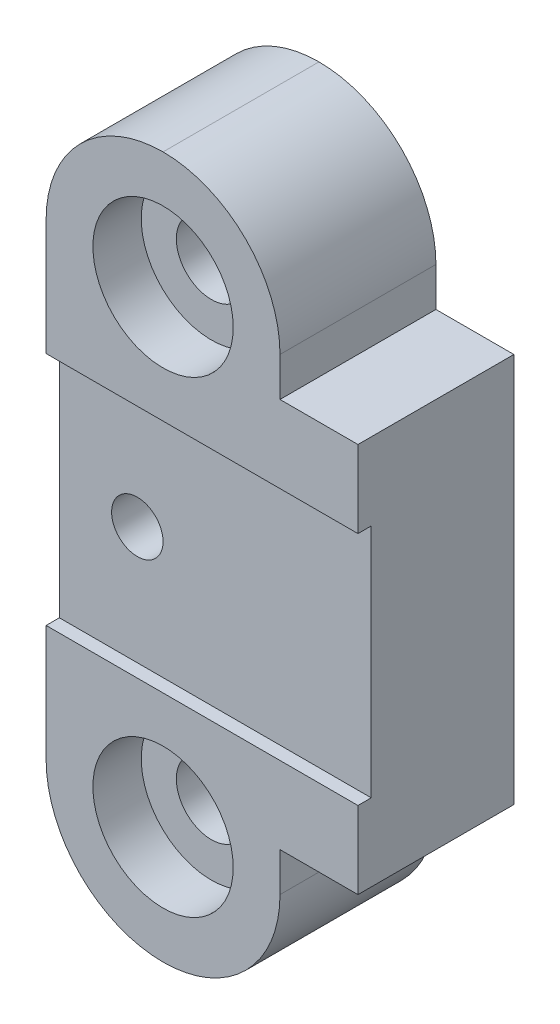
SolidWorks part; units mm, degrees
ref_plane "Ebene vorne" through (0, 0, 0) normal (0, 0, 1) x (1, 0, 0)
ref_plane "Ebene oben" through (0, 0, 0) normal (0, 1, 0) x (1, 0, 0)
ref_plane "Ebene rechts" through (0, 0, 0) normal (1, 0, 0) x (0, 0, -1)
sketch "Skizze1" plane through (0, 0, 0) normal (0, 0, 1) x (1, 0, 0)
  line L0 (0, 0) -> (0, 45)
  line L1 (0, 45) -> (15, 45)
  line L2 (15, 45) -> (15, 35)
  line L3 (15, 35) -> (20, 35)
  line L4 (20, 35) -> (20, 10)
  line L5 (20, 10) -> (15, 10)
  line L6 (15, 10) -> (15, 0)
  line L7 (15, 0) -> (0, 0)
  line L8 (0, 22.5) -> (20, 22.5) construction
  dimension "D1" = 25
  dimension "D2" = 15
  dimension "D3" = 20
  dimension "D4" = 10
extrude "Aufsatz-Linear austragen1" add sketch "Skizze1" along normal blind 10
sketch "Skizze2" plane through (0, 0, 10) normal (0, 0, 1) x (1, 0, 0)
  line L0 (20, 10) -> (20, 35) construction
  line L1 (20, 14.95) -> (0, 14.95)
  line L2 (20, 14.95) -> (20, 30.05)
  line L3 (20, 30.05) -> (0, 30.05)
  line L4 (0, 14.95) -> (0, 30.05)
  line L5 (0, 45) -> (0, 0) construction
  point P8 (0, 22.5)
  point P9 (0, 22.5)
  dimension "D1" = 15.1
extrude "Schnitt-Linear austragen1" cut sketch "Skizze2" against normal blind 0.85
hole_wizard "Stirnsenkung für M4 Flachkopfschraube mit Schlitz1" positions "Skizze6" profile "Skizze7" counterbore size "M4" standard "DIN" end condition through all
sketch "Skizze6" plane through (0, 0, 10) normal (0, 0, 1) x (1, 0, 0)
  line L0 (20, 22.5) -> (0, 22.5) construction
  line L1 (20, 14.95) -> (20, 30.05) construction
  line L2 (0, 30.05) -> (0, 14.95) construction
  line L4 (0, 0) -> (15, 0) construction
  point P0 (7.5, 37.5)
  point P2 (7.5, 7.5)
  point P13 (7.5, 0)
  dimension "D1" = 30
sketch "Skizze7" plane through (7.5, 37.5, 10) normal (1, 0, 0) x (0, -1, 0)
  line L0 (0, 0) -> (0, 10)
  line L1 (0, 10) -> (2.25, 10)
  line L3 (2.25, 10) -> (2.25, 3.1)
  line L4 (2.25, 3.1) -> (4.5, 3.1)
  line L5 (4.5, 3.1) -> (4.5, 0)
  line L7 (4.5, 0) -> (0, 0)
  line L11 (0, -6.35) -> (0, 107.95) construction
  dimension "Bohrerdurchmesser" = 4.5
  dimension "Bohrungstiefe" = 10
  dimension "Senkdurchmesser2" = 9
  dimension "Senktiefe2" = 3.1
hole_wizard "M4 Gewindebohrung1" positions "Skizze9" profile "Skizze10" tap size "M4" standard "DIN" end condition through all
sketch "Skizze9" plane through (0, 0, 9.15) normal (0, 0, 1) x (1, 0, 0)
  line L0 (0, 30.05) -> (0, 14.95) construction
  point P0 (5, 22.5)
  point P2 (0, 0)
  point P5 (0, 22.5)
  dimension "D1" = 5
sketch "Skizze10" plane through (5, 22.5, 9.15) normal (1, 0, 0) x (0, -1, 0)
  line L0 (0, 0) -> (0, 9.15)
  line L1 (0, 9.15) -> (1.65, 9.15)
  line L2 (1.65, 9.15) -> (1.65, 0)
  line L5 (1.65, 0) -> (0, 0)
  line L11 (0, -6.35) -> (0, 107.95) construction
  dimension "Bohrerdurchmesser" = 3.3
  dimension "Bohrungstiefe" = 9.15
cosmetic thread "Bohrungsgewinde1" parameters "D2"=4
fillet "Verrundung1" radius 7.5 4 edges at (0, 0, 5) (15, 0, 5) (15, 45, 5) (0, 45, 5)
